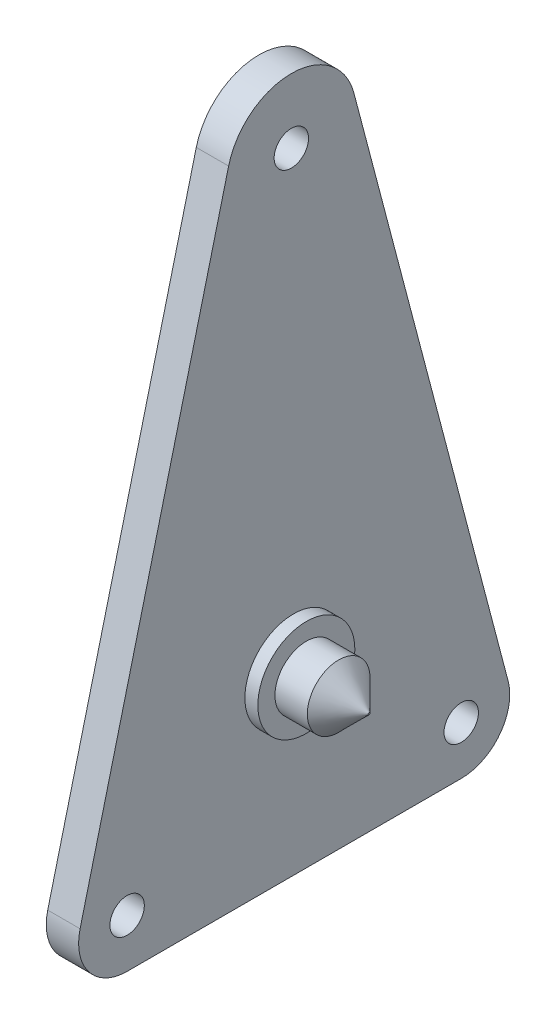
SolidWorks part; units mm, degrees
ref_plane "Front Plane" through (0, 0, 0) normal (0, 0, 1) x (1, 0, 0)
ref_plane "Top Plane" through (0, 0, 0) normal (0, 1, 0) x (1, 0, 0)
ref_plane "Right Plane" through (0, 0, 0) normal (1, 0, 0) x (0, 0, -1)
sketch "Sketch1" plane through (0, 0, 0) normal (1, 0, 0) x (0, 0, -1)
  line L0 (-12.714, 92.0183) -> (-33.8552, 8.5779)
  line L1 (11.8792, 92.1298) -> (33.7761, 8.8845)
  line L2 (-33.8552, 8.5779) -> (-41.8714, -23.0606)
  line L3 (-32.6382, -34.925) -> (32.9452, -34.925)
  line L4 (42.1569, -22.977) -> (33.7761, 8.8845)
  arc A0 (0, -34.925) -> (33.7761, 8.8845) centre (0, 0) ccw construction
  arc A1 (11.8792, 92.1298) -> (-12.714, 92.0183) centre (-0.403, 88.8991) ccw
  arc A2 (33.7761, 8.8845) -> (-33.8552, 8.5779) centre (0, 0) ccw construction
  arc A3 (-12.714, 92.0183) -> (11.8792, 92.1298) centre (-0.403, 88.8991) ccw construction
  circle A4 centre (-0.403, 88.8991) radius 4.7625 construction
  circle A5 centre (0, 0) radius 6.35 construction
  arc A6 (-33.8552, 8.5779) -> (0, -34.925) centre (0, 0) ccw construction
  arc A7 (42.1569, -22.977) -> (32.9452, -34.925) centre (32.9452, -25.4) cw
  arc A8 (-32.6382, -34.925) -> (-41.8714, -23.0606) centre (-32.6382, -25.4) cw
  dimension "D1" = 69.85
  dimension "D2" = 25.4
  dimension "D4" = 9.525
  dimension "D5" = 12.7
  dimension "D6" = 9.525
  dimension "D3" = 88.9
extrude "Boss-Extrude1" add sketch "Sketch1" along normal blind 6.35
sketch "Sketch6" plane through (6.35, 0, 0) normal (1, 0, 0) x (0, 0, -1)
  circle A0 centre (0, 0) radius 9.525
  dimension "D1" = 19.05
extrude "Boss-Extrude4" add sketch "Sketch6" along normal blind 2.54
sketch "Sketch5" plane through (8.89, 0, 0) normal (1, 0, 0) x (0, 0, -1)
  circle A0 centre (0, 0) radius 6.1595
  dimension "D1" = 12.319
extrude "Boss-Extrude3" add sketch "Sketch5" along normal blind 12.319
sketch "Sketch8" plane through (6.35, 0, 0) normal (1, 0, 0) x (0, 0, -1)
  circle A0 centre (-32.6382, -25.4) radius 3.175
  circle A1 centre (32.9452, -25.4) radius 3.175
  circle A2 centre (-0.403, 88.8991) radius 4.7625 construction
  circle A3 centre (-0.403, 88.8991) radius 4.7625 construction
  arc A4 (32.9452, -34.925) -> (42.1569, -22.977) centre (32.9452, -25.4) ccw construction
  arc A5 (-41.8714, -23.0606) -> (-32.6382, -34.925) centre (-32.6382, -25.4) ccw construction
  arc A6 (32.9452, -34.925) -> (42.1569, -22.977) centre (32.9452, -25.4) ccw construction
  arc A7 (-41.8714, -23.0606) -> (-32.6382, -34.925) centre (-32.6382, -25.4) ccw construction
  circle A8 centre (-0.403, 88.8991) radius 3.175
  dimension "D2" = 6.35
  dimension "D1" = 9.525
sketch "Sketch3" [suppressed] plane through (0, 22.225, 0) normal (0, -1, 0) x (1, 0, 0)
  line L0 (6.35, 6.5515) -> (6.35, -6.1485) construction
  line L6 (12.7, 6.5515) -> (12.7, -6.1485) construction
  line L7 (17.78, -6.1485) -> (6.35, -6.1485) construction
  circle A0 centre (12.7, 0.2015) radius 3.175
  point P12 (12.7, 0.2015)
  dimension "D1" = 6.35
  dimension "D2" = 6.35
extrude "Cut-Extrude1" [suppressed] cut sketch "Sketch3" against normal through all
sketch "Sketch4" [suppressed] plane through (17.78, 0, 0) normal (1, 0, 0) x (0, 0, -1)
  line L0 (-6.5515, 45.72) -> (6.1485, 45.72) construction
  line L3 (-0.2015, 50.165) -> (-0.2015, 41.275) construction
  line L4 (2.9735, 50.165) -> (2.9735, 41.275)
  line L5 (-3.3765, 50.165) -> (-3.3765, 41.275)
  line L8 (6.1485, 22.225) -> (6.1485, 66.675) construction
  arc A0 (2.9735, 50.165) -> (-3.3765, 50.165) centre (-0.2015, 50.165) ccw
  arc A1 (-3.3765, 41.275) -> (2.9735, 41.275) centre (-0.2015, 41.275) ccw
  circle A2 centre (-0.2015, 60.325) radius 3.175
  point P5 (-0.2015, 45.72)
  point P8 (-0.2015, 45.72)
  dimension "D4" = 6.35
  dimension "D1" = 41.275
  dimension "D2" = 6.35
  dimension "D3" = 8.89
  dimension "D5" = 19.05
extrude "Cut-Extrude2" [suppressed] cut sketch "Sketch4" against normal through all
chamfer "Chamfer1" distance 5.969 angle 45 1 edges at (21.209, 0, -6.1595)
hole_wizard "1/4 Clearance Hole1" positions "Sketch10" profile "Sketch11" hole size "1/4" standard "ANSI Inch" end condition through all
sketch "Sketch10" plane through (6.35, 0, 0) normal (1, 0, 0) x (0, 0, -1)
  point P0 (-0.403, 88.8991)
  point P3 (32.9452, -25.4)
  point P6 (-32.6382, -25.4)
sketch "Sketch11" plane through (6.35, 88.8991, 0.403) normal (0, 1, 0) x (0, 0, -1)
  line L0 (0, 0) -> (0, 6.35)
  line L1 (0, 6.35) -> (3.3782, 6.35)
  line L2 (3.3782, 6.35) -> (3.3782, 0)
  line L5 (3.3782, 0) -> (0, 0)
  line L11 (0, -6.35) -> (0, 107.95) construction
  dimension "Thru Hole Dia." = 6.7564
  dimension "Thru Hole Depth" = 6.35
